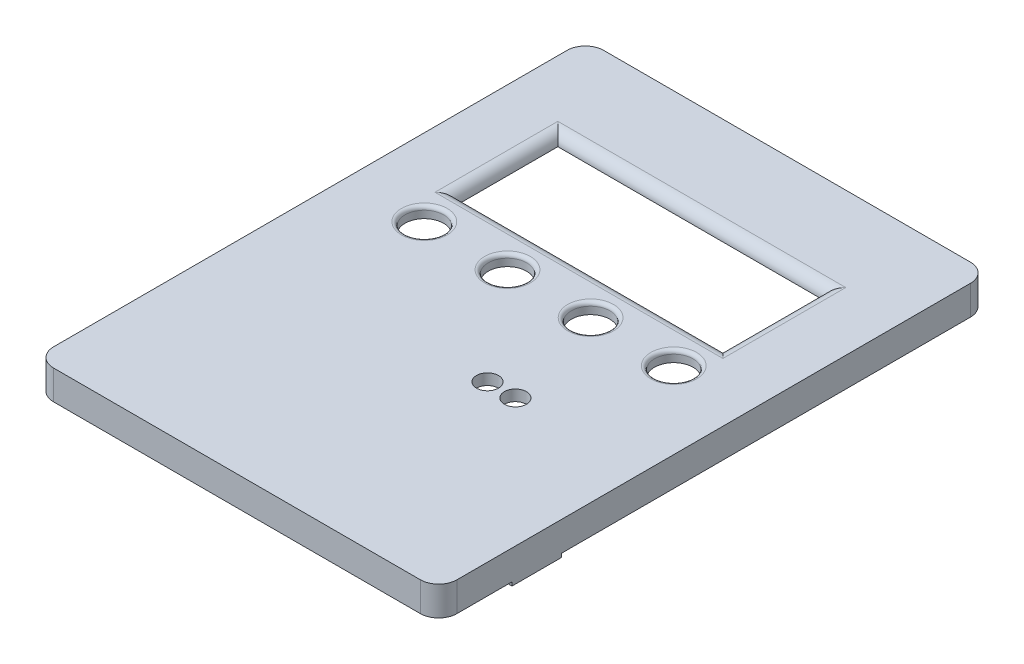
SolidWorks part; units mm, degrees
ref_plane "Plano frontal" through (0, 0, 0) normal (0, 0, 1) x (1, 0, 0)
ref_plane "Plano superior" through (0, 0, 0) normal (0, 1, 0) x (1, 0, 0)
ref_plane "Plano direito" through (0, 0, 0) normal (1, 0, 0) x (0, 0, -1)
sketch "Esboço1" plane through (0, 0, 0) normal (0, 1, 0) x (1, 0, 0)
  line L1 (-55, -75) -> (55, -75)
  line L2 (-55, -75) -> (-55, 75)
  line L3 (-55, 75) -> (55, 75)
  line L4 (55, -75) -> (55, 75)
  line L5 (-55, -75) -> (55, 75) construction
  line L6 (-55, 75) -> (55, -75) construction
  line L10 (0, 0) -> (0, 50000) construction
  point P0 (0, 0)
  dimension "D1" = 150
  dimension "D2" = 110
extrude "Ressalto-extrusão3" add sketch "Esboço1" against normal blind 8
fillet "Filete2" radius 5 4 edges at (-55, -4, -75) (55, -4, -75) (55, -4, 75) (-55, -4, 75)
shell "Casca1" thickness 3 removed face at (0, -8, 0)
sketch "Esboço14" plane through (0, -3, 0) normal (0, -1, 0) x (-1, 0, 0)
  arc A1 (55, 70) -> (50, 75) centre (50, 70) ccw construction
  circle A2 centre (50, -70) radius 5
  circle A3 centre (-50, -70) radius 5
  circle A4 centre (-50, 70) radius 5
  circle A5 centre (50, 70) radius 5
  arc A6 (-50, 75) -> (-55, 70) centre (-50, 70) ccw construction
  arc A7 (-55, -70) -> (-50, -75) centre (-50, -70) ccw construction
  arc A8 (50, -75) -> (55, -70) centre (50, -70) ccw construction
extrude "Ressalto-extrusão7" add sketch "Esboço14" along normal up to surface (5 mm away) up to face at (0, -8, 0)
sketch "Esboço6" plane through (0, 0, 0) normal (0, 1, 0) x (1, 0, 0)
  line L0 (45.4174, -72) -> (-45.4174, -72) construction
  line L1 (-32, -37) -> (32, -37)
  line L2 (-32, -37) -> (-32, -72)
  line L4 (32, -37) -> (32, -72)
  line L5 (-32, -37) -> (32, -72) construction
  line L6 (-32, -72) -> (32, -37) construction
  line L7 (45.4174, -72) -> (-45.4174, -72) construction
  line L14 (-35, -34) -> (-35, -72)
  line L15 (-35, -34) -> (35, -34)
  line L16 (35, -34) -> (35, -72)
  line L17 (-35, -72) -> (-32, -72)
  line L18 (35, -72) -> (32, -72)
  point P0 (0, -54.5)
  dimension "D1" = 64
  dimension "D2" = 35
  dimension "D3" = 3
extrude "Ressalto-extrusão4" add sketch "Esboço6" along normal up to surface (-8 mm away) up to face at (0, -8, 0)
fillet "Filete6" radius 2 4 edges at (-32, -5.5, 72) (-32, -5.5, 37) (32, -5.5, 72) (32, -5.5, 37)
fillet "Filete8" radius 5 4 edges at (35, -5.5, 72) (35, -5.5, 34) (-35, -5.5, 34) (-35, -5.5, 72)
sketch "Esboço8" plane through (0, -8, 0) normal (0, -1, 0) x (-1, 0, 0)
  line L0 (-52, 65.4174) -> (-52, -65.4174) construction
  line L1 (-52, -41.5) -> (-55, -41.5)
  line L2 (-52, -41.5) -> (-52, -55)
  line L3 (-52, -55) -> (-55, -55)
  line L4 (-55, -41.5) -> (-55, -55)
  line L5 (-55, -70) -> (-55, 70) construction
  line L6 (50, -75) -> (-50, -75) construction
  dimension "D1" = 13.5
  dimension "D2" = 20
sketch "Esboço15" plane through (0, -8, 0) normal (0, -1, 0) x (1, 0, 0)
  circle A0 centre (-50, -70) radius 1.7
  circle A1 centre (50, -70) radius 1.7
  circle A2 centre (50, 70) radius 1.7
  circle A3 centre (-50, 70) radius 1.7
  dimension "D1" = 3.4
extrude "Corte-extrusão3" cut sketch "Esboço15" against normal offset from surface (3 mm away) 5 up to face at (0, 0, 0)
sketch "Esboço18" plane through (0, 0, 0) normal (0, 1, 0) x (1, 0, 0)
  line L0 (-55, 70) -> (-55, -70) construction
  line L1 (55, -70) -> (55, 70) construction
  line L2 (-50, -75) -> (50, -75) construction
  circle A0 centre (-34, 10.1) radius 5.25
  circle A1 centre (-11.3333, 10.1) radius 5.25
  circle A2 centre (11.3333, 10.1) radius 5.25
  circle A3 centre (34, 10.1) radius 5.25
  dimension "D2" = 10.5
  dimension "D3" = 21
  dimension "D4" = 21
  dimension "D5" = 85.1
  dimension "D1" = 4
extrude "Corte-extrusão7" cut sketch "Esboço18" against normal blind 5
sketch "Esboço19" plane through (0, 0, 0) normal (0, 1, 0) x (1, 0, 0)
  line L0 (-50, -75) -> (50, -75) construction
  line L1 (-36.5, 49) -> (36, 49)
  line L2 (-36.5, 49) -> (-36.5, 21.5)
  line L3 (-36.5, 21.5) -> (36, 21.5)
  line L4 (36, 49) -> (36, 21.5)
  line L5 (50, 75) -> (-50, 75) construction
  line L6 (55, -70) -> (55, 70) construction
  line L7 (-55, 70) -> (-55, -70) construction
  dimension "D1" = 96.5
  dimension "D2" = 26
  dimension "D3" = 19
  dimension "D4" = 18.5
extrude "Corte-extrusão8" cut sketch "Esboço19" against normal blind 5
fillet "Filete9" radius 3 4 edges at (36, 0, -35.25) (-0.25, 0, -49) (-36.5, 0, -35.25) (-0.25, 0, -21.5)
fillet "Filete10" radius 1 4 edges at (11.3333, 0, -4.85) (34, 0, -4.85) (-11.3333, 0, -4.85) (-34, 0, -4.85)
sketch "Esboço20" plane through (0, 0, 0) normal (0, 1, 0) x (1, 0, 0)
  circle A0 centre (12.42, -19.11) radius 3
  circle A1 centre (20.04, -19.11) radius 3
extrude "Corte-extrusão9" cut sketch "Esboço20" against normal blind 10
sketch "Esboço22" plane through (-55, 0, 0) normal (-1, 0, 0) x (0, 0, 1)
  line L0 (-70, -8) -> (70, -8) construction
  line L1 (7.35, -2.5) -> (20.87, -2.5)
  line L2 (7.35, -2.5) -> (7.35, -11.5651)
  line L3 (7.35, -11.5651) -> (20.87, -11.5651)
  line L4 (20.87, -2.5) -> (20.87, -11.5651)
  dimension "D1" = 54.13
  dimension "D2" = 82.35
  dimension "D3" = 5.5
extrude "Corte-extrusão11" cut sketch "Esboço22" against normal blind 20
extrude "Ressalto-extrusão9" add sketch "Esboço8" along normal blind 1
equation "\"D_BasePCB\"= 8mm"
